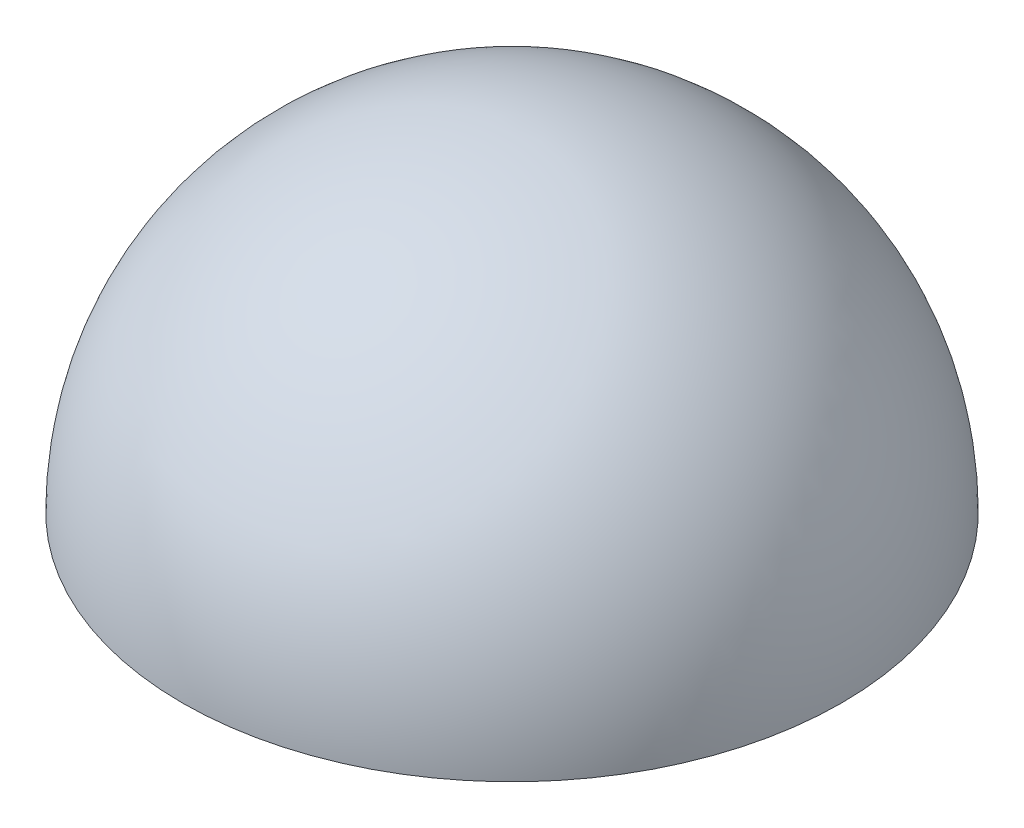
SolidWorks part; units mm, degrees
ref_plane "Front Plane" through (0, 0, 0) normal (0, 0, 1) x (1, 0, 0)
ref_plane "Top Plane" through (0, 0, 0) normal (0, 1, 0) x (1, 0, 0)
ref_plane "Right Plane" through (0, 0, 0) normal (1, 0, 0) x (0, 0, -1)
sketch "Sketch1" plane through (0, 0, 0) normal (0, 0, 1) x (1, 0, 0)
  line L0 (-15, 0) -> (15, 0)
  line L1 (0, -1000) -> (0, 49000) construction
  arc A0 (15, 0) -> (-15, 0) centre (0, 0) ccw
  dimension "D1" = 15
revolve "Revolve1" add sketch "Sketch1" angle 360 about L1 region at (-6.3662, 6.3662, 0)
sketch "Sketch2" plane through (0, 0, 0) normal (0, -1, 0) x (1, 0, 0)
  line L1 (4.8786, -8.45) -> (9.7572, 0)
  line L2 (9.7572, 0) -> (4.8786, 8.45)
  line L3 (4.8786, 8.45) -> (-4.8786, 8.45)
  line L4 (-4.8786, 8.45) -> (-9.7572, 0)
  line L5 (-9.7572, 0) -> (-4.8786, -8.45)
  line L6 (-4.8786, -8.45) -> (4.8786, -8.45)
  circle A0 centre (0, 0) radius 8.45 construction
  dimension "D1" = 16.9
extrude "Cut-Extrude2" cut sketch "Sketch2" against normal blind 3.5
sketch "Sketch3" plane through (0, 3.5, 0) normal (0, -1, 0) x (1, 0, 0)
  line L0 (-4.8786, 8.45) -> (-9.7572, 0) construction
  line L1 (3.7239, -6.45) -> (7.4478, 0)
  line L2 (7.4478, 0) -> (3.7239, 6.45)
  line L3 (3.7239, 6.45) -> (-3.7239, 6.45)
  line L4 (-3.7239, 6.45) -> (-7.4478, 0)
  line L5 (-7.4478, 0) -> (-3.7239, -6.45)
  line L6 (-3.7239, -6.45) -> (3.7239, -6.45)
  circle A0 centre (0, 0) radius 5.1
  circle A1 centre (0, 0) radius 6.45 construction
  dimension "D1" = 10.2
  dimension "D2" = 2
extrude "Cut-Extrude4" cut sketch "Sketch3" against normal blind 2 contours L3 L4 L5 L6 L1 L2
sketch "Sketch4" plane through (0, 0, 0) normal (1, 0, 0) x (0, 0, -1)
  line L0 (-6.45, 5.5) -> (0, 5.5)
  line L1 (0, 5.5) -> (0, 13.5)
  line L2 (0, 5.5) -> (-6.45, 5.5) construction
  ellipse E0 centre (0, 5.5) end of major axis (0, 13.5) minor radius 6.45 (0, 13.5) -> (-6.45, 5.5) ccw
  dimension "D1" = 8
revolve "Cut-Revolve1" cut sketch "Sketch4" angle 360 about L1
sketch "Sketch7" plane through (0, 0, 0) normal (0, -1, 0) x (1, 0, 0)
  line L0 (861.1657, -497.1943) -> (-42197.1217, 24362.5196) construction
  line L1 (-861.1657, -497.1943) -> (42197.1217, 24362.5196) construction
  line L2 (0, 0) -> (0, -49719.4277) construction
  circle A0 centre (-9.9593, 5.75) radius 1.5
  circle A1 centre (9.9593, 5.75) radius 1.5
  circle A2 centre (0, -11.5) radius 1.5
  point P16 (0, 0)
  dimension "D1" = 3
  dimension "D3" = 3
  dimension "D2" = 11.5
  dimension "D4" = 60
  dimension "D5" = 60
extrude "Cut-Extrude6" cut sketch "Sketch7" against normal blind 7
sketch "Sketch8" plane through (0, 0, 0) normal (0, -1, 0) x (1, 0, 0)
  line L1 (-8.4293, 3.1) -> (-6.8993, 5.75)
  line L2 (-6.8993, 5.75) -> (-8.4293, 8.4)
  line L3 (-8.4293, 8.4) -> (-11.4893, 8.4)
  line L4 (-11.4893, 8.4) -> (-13.0192, 5.75)
  line L5 (-13.0192, 5.75) -> (-11.4893, 3.1)
  line L6 (-11.4893, 3.1) -> (-8.4293, 3.1)
  line L24 (6.8993, 5.75) -> (8.4293, 3.1)
  line L25 (8.4293, 3.1) -> (11.4893, 3.1)
  line L26 (11.4893, 3.1) -> (13.0192, 5.75)
  line L27 (13.0192, 5.75) -> (11.4893, 8.4)
  line L28 (11.4893, 8.4) -> (8.4293, 8.4)
  line L29 (8.4293, 8.4) -> (6.8993, 5.75)
  line L30 (1.53, -8.85) -> (-1.53, -8.85)
  line L31 (-1.53, -8.85) -> (-3.06, -11.5)
  line L32 (-3.06, -11.5) -> (-1.53, -14.15)
  line L33 (-1.53, -14.15) -> (1.53, -14.15)
  line L34 (1.53, -14.15) -> (3.06, -11.5)
  line L35 (3.06, -11.5) -> (1.53, -8.85)
  circle A0 centre (-9.9593, 5.75) radius 2.65 construction
  circle A1 centre (9.9593, 5.75) radius 2.65 construction
  circle A2 centre (0, -11.5) radius 2.65 construction
  point P10 (5.4486, 15.9529)
  point P11 (0, 0)
  point P27 (0, 0)
  dimension "D1" = 5.3
  dimension "D2" = 3
extrude "Cut-Extrude7" cut sketch "Sketch8" against normal blind 2.2
